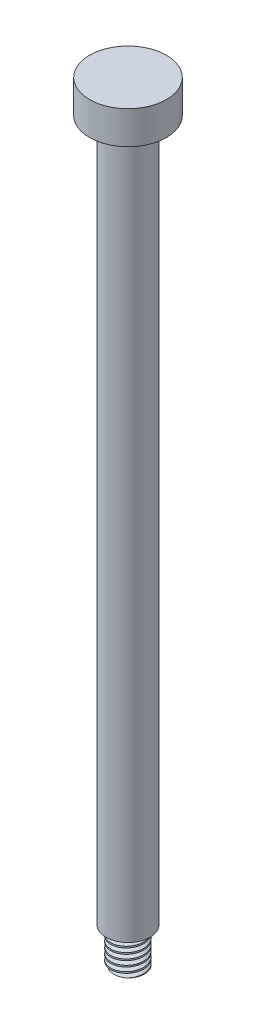
SolidWorks part; units mm, degrees
material "AISI 321 Acero inoxidable recocido (SS)"
ref_plane "Alzado" through (0, 0, 0) normal (0, 0, 1) x (1, 0, 0)
ref_plane "Planta" through (0, 0, 0) normal (0, 1, 0) x (1, 0, 0)
ref_plane "Vista lateral" through (0, 0, 0) normal (1, 0, 0) x (0, 0, -1)
sketch "Croquis1" plane through (0, 0, 0) normal (0, 1, 0) x (1, 0, 0)
  circle A0 centre (0, 0) radius 6.35
  dimension "D1" = 12.7
extrude "Saliente-Extruir1" add sketch "Croquis1" along normal blind 202.7
sketch "Croquis2" plane through (0, 202.7, 0) normal (0, 1, 0) x (1, 0, 0)
  circle A0 centre (0, 0) radius 11.1125
  dimension "D1" = 22.225
extrude "Saliente-Extruir2" add sketch "Croquis2" along normal blind 9.525
sketch "Croquis3" plane through (0, 0, 0) normal (0, -1, 0) x (1, 0, 0)
  circle A0 centre (0, 0) radius 4.7625
  dimension "D1" = 9.525
extrude "Saliente-Extruir3" add sketch "Croquis3" along normal blind 10
sketch "Croquis4" plane through (0, -10, 0) normal (0, -1, 0) x (1, 0, 0)
  circle A0 centre (0, 0) radius 4.7625
  circle A1 centre (0, 0) radius 4.7625 construction
curve "Hélice/Espiral1" pitch 1.5875 height 11.1125 turns 7
sketch "Croquis5" plane through (0, 0, 0) normal (0, 0, 1) x (1, 0, 0)
  line L0 (-4.7625, -10.5774) -> (-4.7625, -9.4226)
  line L1 (-4.7625, 0) -> (-4.7625, -10) construction
  line L2 (-4.7625, -9.4226) -> (-3.7625, -10)
  line L3 (-4.7625, -10) -> (4.7625, -10) construction
  line L4 (-3.7625, -10) -> (-4.7625, -10.5774)
  line L5 (-3.7625, -10) -> (-4.7625, -10) construction
  dimension "D1" = 60
  dimension "D2" = 1
sweep "Cortar-Barrer1" cut profiles "Croquis5" path "Hélice/Espiral1" align with end faces yes
